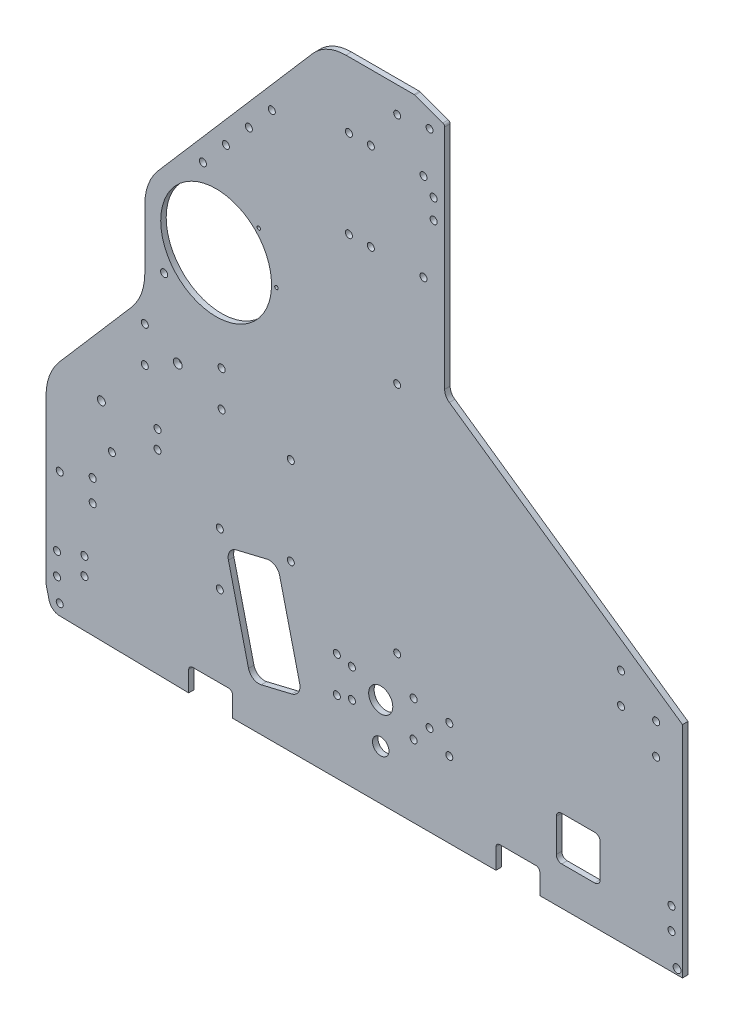
SolidWorks part; units mm, degrees
ref_plane "Front Plane" through (0, 0, 0) normal (0, 0, 1) x (1, 0, 0)
ref_plane "Top Plane" through (0, 0, 0) normal (0, 1, 0) x (1, 0, 0)
ref_plane "Right Plane" through (0, 0, 0) normal (1, 0, 0) x (0, 0, -1)
sketch "Sketch1" plane through (0, 0, 0) normal (0, 0, 1) x (1, 0, 0)
  line L0 (82.55, -20.32) -> (82.55, -6.35)
  line L2 (0, 0) -> (0, 157.48)
  line L4 (368.3, -20.32) -> (368.3, 106.68)
  line L5 (82.55, -6.35) -> (107.95, -6.35)
  line L6 (107.95, -6.35) -> (107.95, -20.32)
  line L7 (107.95, -20.32) -> (260.35, -20.32)
  line L8 (260.35, -20.32) -> (260.35, -6.35)
  line L9 (260.35, -6.35) -> (285.75, -6.35)
  line L10 (285.75, -6.35) -> (285.75, -20.32)
  line L11 (285.75, -20.32) -> (368.3, -20.32)
  line L12 (361.95, 12.7) -> (368.3, 12.7) construction
  line L13 (0, 0) -> (6.35, 0) construction
  line L14 (0.1896, -7.8901) -> (1.7771, -14.2401)
  line L15 (7.8295, -19.0491) -> (82.55, -20.32)
  line L16 (0, 0) -> (0, -6.35)
  line L17 (76.2, 141.605) -> (79.375, 141.605) construction
  line L18 (57.15, 131.2863) -> (101.6, 131.2862) construction
  line L19 (57.15, 131.2863) -> (57.15, 151.9238) construction
  line L20 (101.6, 131.2862) -> (101.6, 151.9237) construction
  line L21 (57.15, 151.9238) -> (101.6, 151.9237) construction
  line L22 (57.15, 131.2863) -> (101.6, 151.9237) construction
  line L23 (101.6, 131.2862) -> (57.15, 151.9238) construction
  line L25 (203.2, 59.805) -> (203.2, 194.805) construction
  line L26 (203.2, 194.805) -> (203.2, 329.805) construction
  line L27 (355.6, 332.105) -> (330.2, 332.105) construction
  line L28 (330.2, 332.105) -> (330.2, 217.805) construction
  line L29 (330.2, 217.805) -> (355.6, 217.805) construction
  line L30 (355.6, 217.805) -> (355.6, 332.105) construction
  line L31 (203.2, 344.805) -> (203.2, 194.805) construction
  line L32 (50.8, 332.105) -> (76.2, 332.105) construction
  line L33 (76.2, 332.105) -> (76.2, 217.805) construction
  line L34 (50.8, 217.805) -> (50.8, 332.105) construction
  line L35 (76.2, 217.805) -> (50.8, 217.805) construction
  line L36 (213.2, 344.805) -> (230.6638, 338.455)
  line L37 (203.2, 344.805) -> (161.925, 344.805)
  line L38 (203.2, 344.805) -> (213.2, 344.805)
  line L39 (348.5362, 344.805) -> (413.4623, 344.805)
  line L40 (348.5362, 344.805) -> (230.6638, 344.805) construction
  line L42 (161.925, 344.805) -> (0, 157.48)
  line L44 (230.6638, 338.455) -> (230.6638, 202.565)
  line L45 (230.6638, 202.565) -> (368.3, 106.68)
  line L46 (213.2, 344.805) -> (-141.0713, 344.805) construction
  circle A0 centre (6.35, 0) radius 2.032
  circle A1 centre (6.35, 12.7) radius 2.032
  circle A2 centre (361.95, 0) radius 2.032
  circle A3 centre (361.95, 12.7) radius 2.032
  arc A5 (1.7771, -14.2401) -> (7.8295, -19.0491) centre (7.9375, -12.7) ccw
  circle A6 centre (7.9375, -12.7) radius 2.032
  arc A7 (0, -6.35) -> (0.1896, -7.8901) centre (6.35, -6.35) ccw
  circle A8 centre (38.1, 78.105) radius 2.032
  circle A9 centre (76.2, 141.605) radius 2.54
  circle A10 centre (101.6, 131.2862) radius 2.032
  circle A11 centre (101.6, 151.9237) radius 2.032
  circle A12 centre (57.15, 151.9238) radius 2.032
  circle A13 centre (57.15, 131.2863) radius 2.032
  circle A15 centre (203.2, 59.805) radius 2
  circle A16 centre (203.2, 194.805) radius 2
  circle A17 centre (203.2, 329.805) radius 2
  circle A18 centre (63.5, 313.055) radius 2.032
  circle A20 centre (355.6, 332.105) radius 2.032
  circle A21 centre (330.2, 332.105) radius 2.032
  circle A22 centre (355.6, 217.805) radius 2.032
  circle A23 centre (330.2, 217.805) radius 2.032
  circle A24 centre (50.8, 332.105) radius 2.032
  circle A25 centre (76.2, 332.105) radius 2.032
  circle A26 centre (50.8, 217.805) radius 2.032
  circle A27 centre (76.2, 217.805) radius 2.032
  circle A28 centre (221.9319, 332.105) radius 2
  circle A29 centre (224.3138, 298.831) radius 2.032
  circle A30 centre (353.06, 100.7351) radius 2.032
  circle A31 centre (332.74, 115.9751) radius 2.032
  circle A32 centre (332.74, 98.1951) radius 2.032
  circle A33 centre (353.06, 82.9551) radius 2.032
  circle A34 centre (117.3562, 280.4276) radius 2.032
  circle A35 centre (104.0678, 265.0548) radius 2.032
  circle A36 centre (90.7795, 249.682) radius 2.032
  circle A38 centre (130.6445, 295.8004) radius 2.032
  circle A39 centre (68.326, 182.9237) radius 2.032
  circle A40 centre (224.3138, 287.401) radius 2.032
  point P82 (203.2, 344.805)
  point P83 (221.9319, 341.63)
  point P90 (368.3, 62.484)
  dimension "D6" = 4.064
  dimension "D10" = 6.35
  dimension "D11" = 4.064
  dimension "D17" = 38.1
  dimension "D27" = 4
  dimension "D31" = 4.064
  dimension "D32" = 41.275
  dimension "D36" = 4.064
  dimension "D47" = 39.624
  dimension "D48" = 4.064
  dimension "D25" = 5.08
  dimension "D26" = 4.064
  dimension "D52" = 4.064
  dimension "D65" = 4.064
  dimension "D2" = 127
  dimension "D3" = 13.97
  dimension "D4" = 25.4
  dimension "D5" = 152.4
  dimension "D7" = 12.7
  dimension "D8" = 6.35
  dimension "D9" = 20.32
  dimension "D12" = 12.7
  dimension "D13" = 1.5875
  dimension "D14" = 82.55
  dimension "D15" = 368.3
  dimension "D16" = 6.35
  dimension "D18" = 98.425
  dimension "D19" = 38.1
  dimension "D20" = 63.5
  dimension "D21" = 3.175
  dimension "D22" = 270
  dimension "D23" = 20.6375
  dimension "D24" = 44.45
  dimension "D28" = 135
  dimension "D29" = 12.7
  dimension "D30" = 15
  dimension "D33" = 63.5
  dimension "D34" = 27.4638
  dimension "D35" = 12.7
  dimension "D37" = 114.3
  dimension "D38" = 25.4
  dimension "D39" = 12.7
  dimension "D40" = 157.48
  dimension "D41" = 142.24
  dimension "D42" = 365.125
  dimension "D43" = 10
  dimension "D44" = 6.35
  dimension "D45" = 31.75
  dimension "D46" = 6.35
  dimension "D49" = 6.35
  dimension "D50" = 203.2
  dimension "D51" = 15.24
  dimension "D53" = 17.78
  dimension "D54" = 17.78
  dimension "D55" = 20.32
  dimension "D56" = 15.24
  dimension "D57" = 92.202
  dimension "D58" = 8.382
  dimension "D59" = 20.32
  dimension "D60" = 20.32
  dimension "D61" = 8.382
  dimension "D62" = 20.32
  dimension "D63" = 8.382
  dimension "D64" = 8.382
  dimension "D66" = 35.052
  dimension "D67" = 68.326
  dimension "D68" = 11.43
extrude "Boss-Extrude1" add sketch "Sketch1" along normal blind 3.175 contours L16 A7 L14 A5 L15 L2 A0 A1 A6 region at (171.3489, 119.5243, 0)
fillet "Fillet1" radius 2.286 4 edges at (285.75, -6.35, 1.5875) (107.95, -6.35, 1.5875) (260.35, -6.35, 1.5875) (82.55, -6.35, 1.5875)
fillet "Fillet2" radius 6.35 1 edges at (230.6638, 202.565, 1.5875)
sketch "Sketch2" plane through (0, 0, 0) normal (0, 0, -1) x (-1, 0, 0)
  circle A0 centre (-100.5528, 71.086) radius 2.032 construction
  circle A1 centre (-100.5528, 40.606) radius 2.032 construction
  circle A2 centre (-22.225, 18.2025) radius 2.032 construction
  circle A3 centre (-22.225, 8.0425) radius 2.032 construction
  circle A4 centre (-100.5528, 71.086) radius 2.032
  circle A5 centre (-100.5528, 40.606) radius 2.032
  circle A6 centre (-22.225, 18.2025) radius 2.032
  circle A7 centre (-22.225, 8.0425) radius 2.032
extrude "Cut-Extrude1" cut sketch "Sketch2" against normal through all
fillet "Fillet3" radius 1.5875 2 edges at (230.6638, 338.455, 1.5875) (213.2, 344.805, 1.5875)
sketch "Sketch3" plane through (0, 0, 3.175) normal (0, 0, 1) x (1, 0, 0)
  line L0 (132.9524, 63.2646) -> (132.7215, 64.2281) construction
  line L1 (128.3814, 66.8897) -> (110.6828, 62.6472) construction
  line L2 (114.5132, 58.4237) -> (126.8822, 61.3887) construction
  line L3 (108.0212, 58.3071) -> (108.2522, 57.3436) construction
  line L4 (131.2006, 57.703) -> (140.0164, 20.9265) construction
  line L5 (144.0993, 16.7636) -> (132.9524, 63.2646) construction
  line L6 (108.2522, 57.3436) -> (119.3991, 10.8426) construction
  line L7 (121.1509, 16.4042) -> (112.3351, 53.1807) construction
  line L8 (119.3991, 10.8426) -> (119.6301, 9.8791) construction
  line L9 (144.3303, 15.8001) -> (144.0993, 16.7636) construction
  line L10 (137.8383, 15.6835) -> (125.4694, 12.7185) construction
  line L11 (123.9701, 7.2175) -> (141.6687, 11.4601) construction
  line L12 (132.9524, 63.2646) -> (132.7215, 64.2281)
  line L13 (128.3814, 66.8897) -> (110.6828, 62.6472)
  line L14 (114.5132, 58.4237) -> (126.8822, 61.3887)
  line L15 (108.0212, 58.3071) -> (108.2522, 57.3436)
  line L16 (131.2006, 57.703) -> (140.0164, 20.9265)
  line L17 (144.0993, 16.7636) -> (132.9524, 63.2646)
  line L18 (108.2522, 57.3436) -> (119.3991, 10.8426)
  line L19 (121.1509, 16.4042) -> (112.3351, 53.1807)
  line L20 (119.3991, 10.8426) -> (119.6301, 9.8791)
  line L21 (144.3303, 15.8001) -> (144.0993, 16.7636)
  line L22 (137.8383, 15.6835) -> (125.4694, 12.7185)
  line L23 (123.9701, 7.2175) -> (141.6687, 11.4601)
  line L24 (127.7894, 69.3598) -> (110.0908, 65.1172)
  line L25 (105.5512, 57.715) -> (105.7822, 56.7515)
  line L26 (105.7822, 56.7515) -> (116.9291, 10.2505)
  line L27 (116.9291, 10.2505) -> (117.16, 9.287)
  line L28 (124.5622, 4.7475) -> (142.2608, 8.99)
  line L29 (146.8003, 16.3922) -> (146.5694, 17.3557)
  line L30 (146.5694, 17.3557) -> (135.4225, 63.8567)
  line L31 (135.4225, 63.8567) -> (135.1915, 64.8202)
  line L32 (14.605, -0.1369) -> (103.7278, 32.3011) construction
  line L33 (14.605, -0.1369) -> (103.7278, 32.3011)
  line L34 (0, -6.35) -> (0, 157.48) construction
  line L35 (-39.6666, 74.7152) -> (103.7278, 126.9065) construction
  line L36 (26.9875, 46.9531) -> (26.9875, 59.6531) construction
  line L37 (107.95, -20.32) -> (260.35, -20.32) construction
  line L38 (64.5259, 92.5258) -> (64.5259, 102.9405) construction
  arc A0 (132.7215, 64.2281) -> (128.6308, 66.9403) centre (129.2206, 63.3889) ccw construction
  arc A1 (110.6828, 62.6472) -> (110.4377, 62.5791) centre (111.522, 59.1463) ccw construction
  arc A2 (128.6308, 66.9403) -> (128.3814, 66.8897) centre (129.2206, 63.3889) ccw construction
  arc A3 (110.4377, 62.5791) -> (108.0212, 58.3071) centre (111.522, 59.1463) ccw construction
  arc A4 (119.6301, 9.8791) -> (123.7207, 7.1669) centre (123.1309, 10.7183) ccw construction
  arc A5 (141.9139, 11.5281) -> (144.3303, 15.8001) centre (140.8295, 14.9609) ccw construction
  arc A6 (141.6687, 11.4601) -> (141.9139, 11.5281) centre (140.8295, 14.9609) ccw construction
  arc A7 (123.7207, 7.1669) -> (123.9701, 7.2175) centre (123.1309, 10.7183) ccw construction
  arc A8 (132.7215, 64.2281) -> (128.6308, 66.9403) centre (129.2206, 63.3889) ccw
  arc A9 (110.6828, 62.6472) -> (110.4377, 62.5791) centre (111.522, 59.1463) ccw
  arc A10 (128.6308, 66.9403) -> (128.3814, 66.8897) centre (129.2206, 63.3889) ccw
  arc A11 (110.4377, 62.5791) -> (108.0212, 58.3071) centre (111.522, 59.1463) ccw
  arc A12 (119.6301, 9.8791) -> (123.7207, 7.1669) centre (123.1309, 10.7183) ccw
  arc A13 (141.9139, 11.5281) -> (144.3303, 15.8001) centre (140.8295, 14.9609) ccw
  arc A14 (141.6687, 11.4601) -> (141.9139, 11.5281) centre (140.8295, 14.9609) ccw
  arc A15 (123.7207, 7.1669) -> (123.9701, 7.2175) centre (123.1309, 10.7183) ccw
  arc A16 (110.0908, 65.1172) -> (109.6726, 65.0012) centre (111.522, 59.1463) ccw
  arc A17 (109.6726, 65.0012) -> (105.5512, 57.715) centre (111.522, 59.1463) ccw
  arc A18 (117.16, 9.287) -> (124.1369, 4.6613) centre (123.1309, 10.7183) ccw
  arc A19 (124.1369, 4.6613) -> (124.5622, 4.7475) centre (123.1309, 10.7183) ccw
  arc A20 (142.2608, 8.99) -> (142.6789, 9.1061) centre (140.8295, 14.9609) ccw
  arc A21 (142.6789, 9.1061) -> (146.8003, 16.3922) centre (140.8295, 14.9609) ccw
  arc A22 (135.1915, 64.8202) -> (128.2147, 69.446) centre (129.2206, 63.3889) ccw
  arc A23 (128.2147, 69.446) -> (127.7894, 69.3598) centre (129.2206, 63.3889) ccw
  circle A26 centre (133.35, 208.2281) radius 1.016 construction
  circle A33 centre (26.9875, 46.9531) radius 2.032
  circle A34 centre (26.9875, 59.6531) radius 2.032
  circle A35 centre (7.9375, 53.3031) radius 2.032
  circle A37 centre (32.0306, 100.8109) radius 31.75 construction
  circle A38 centre (32.0306, 100.8109) radius 2.286
  circle A39 centre (123.1207, 232.9238) radius 1.016 construction
  circle A40 centre (64.5259, 102.9405) radius 2.032
  circle A41 centre (64.5259, 92.5258) radius 2.032
  circle A42 centre (133.35, 208.2281) radius 1.016
  circle A43 centre (123.1207, 232.9238) radius 1.016
  ellipse E0 centre (124.5974, 48.8487) end of major axis (128.5376, 61.3578) minor radius 6 (131.2006, 57.703) -> (126.8822, 61.3887) ccw construction
  ellipse E1 centre (122.2349, 48.2824) end of major axis (113.0518, 57.6456) minor radius 6 (114.5132, 58.4237) -> (112.3351, 53.1807) ccw construction
  ellipse E2 centre (127.7541, 25.2585) end of major axis (131.6942, 37.7675) minor radius 6 (121.1509, 16.4042) -> (125.4694, 12.7185) ccw construction
  ellipse E3 centre (130.1166, 25.8248) end of major axis (139.2998, 16.4616) minor radius 6 (137.8383, 15.6835) -> (140.0164, 20.9265) ccw construction
  ellipse E4 centre (124.5974, 48.8487) end of major axis (120.6573, 36.3397) minor radius 6 (131.2006, 57.703) -> (126.8822, 61.3887) ccw
  ellipse E5 centre (122.2349, 48.2824) end of major axis (131.4181, 38.9192) minor radius 6 (114.5132, 58.4237) -> (112.3351, 53.1807) ccw
  ellipse E6 centre (127.7541, 25.2585) end of major axis (131.6942, 37.7675) minor radius 6 (121.1509, 16.4042) -> (125.4694, 12.7185) ccw
  ellipse E7 centre (130.1166, 25.8248) end of major axis (139.2998, 16.4616) minor radius 6 (137.8383, 15.6835) -> (140.0164, 20.9265) ccw
  point P93 (26.9875, 53.3031)
  point P115 (32.0306, 100.8109)
  dimension "D3" = 63.5
  dimension "D4" = 4.572
  dimension "D8" = 4.064
  dimension "D2" = 88.9
  dimension "D5" = 7.9375
  dimension "D6" = 19.05
  dimension "D7" = 73.6231
  dimension "D9" = 12.7
  dimension "D10" = 10.4147
  dimension "D11" = 37.5384
  dimension "D12" = 45.5727
  dimension "D1" = 2.54
extrude "Cut-Extrude2" cut sketch "Sketch3" against normal through all contours A22 A23 L24 A16 A17 L25 L26 L27 A18 A19 L28 A20 A21 L29 L30 L31 A15 A12 L20 L18 L15 A11 A9 L13 A10 A8 L12 L17 L21 A13 A14 L23 | A12 A15 L23 A14 A13 L21 L17 L12 A8 A10 L13 A9 A11 L15 L18 L20 E7 L22 E6 L19 E5 L14 E4 L16 | L22 E7 L16 E4 L14 E5 L19 E6 | A38 | A41 | A40 | A35 | A34 | A33 | A43 | A42 region at (137.844, 39.8506, 3.175) region at (126.1758, 37.0536, 3.175) region at (128.1544, 68.6507, 3.175) region at (32.0306, 100.8109, 3.175) region at (64.5259, 102.9405, 3.175) region at (64.5259, 92.5258, 3.175)
sketch "Sketch4" plane through (0, 0, 3.175) normal (0, 0, 1) x (1, 0, 0)
  line L0 (57.15, 151.9238) -> (101.6, 151.9237) construction
  line L1 (168.275, 21.4312) -> (212.725, 21.4312) construction
  line L2 (168.275, 21.4312) -> (168.275, 42.0687) construction
  line L3 (168.275, 42.0687) -> (212.725, 42.0687) construction
  line L4 (212.725, 21.4312) -> (212.725, 42.0687) construction
  line L5 (168.275, 21.4312) -> (212.725, 42.0687) construction
  line L6 (168.275, 42.0687) -> (212.725, 21.4312) construction
  line L7 (57.15, 131.2863) -> (57.15, 151.9238) construction
  line L8 (107.95, -20.32) -> (260.35, -20.32) construction
  line L9 (193.675, 31.75) -> (177.005, 31.75) construction
  line L10 (190.5, 31.75) -> (193.675, 31.75) construction
  line L11 (6.35, 12.7) -> (361.95, 12.7) construction
  line L12 (107.95, -6.35) -> (107.95, -20.32) construction
  line L13 (193.675, 31.75) -> (220.6625, 31.75) construction
  line L14 (177.005, 23.4569) -> (177.005, 40.0431) construction
  line L15 (213.2, 44.805) -> (193.2, 44.805) construction
  line L16 (213.2, 44.805) -> (213.2, 344.805) construction
  line L17 (213.2, 344.805) -> (193.2, 344.805) construction
  line L18 (193.2, 44.805) -> (193.2, 344.805) construction
  line L19 (213.2, 44.805) -> (193.2, 344.805) construction
  line L20 (213.2, 344.805) -> (193.2, 44.805) construction
  line L21 (226.9319, 332.105) -> (226.9319, 31.75) construction
  line L22 (237.33, 40.0431) -> (233.3612, 40.0431) construction
  line L23 (237.33, 23.4569) -> (233.3612, 23.4569) construction
  circle A0 centre (168.275, 42.0687) radius 2.032
  circle A1 centre (212.725, 42.0687) radius 2.032
  circle A2 centre (212.725, 21.4312) radius 2.032
  circle A3 centre (168.275, 21.4312) radius 2.032
  circle A4 centre (193.675, 31.75) radius 6.985
  circle A7 centre (220.6625, 31.75) radius 14.2875 construction
  circle A8 centre (193.675, 31.75) radius 12.7 construction
  circle A9 centre (177.005, 40.0431) radius 2.032
  circle A10 centre (177.005, 23.4569) radius 2.032
  circle A11 centre (237.33, 40.0431) radius 2.032 construction
  circle A12 centre (237.33, 23.4569) radius 2.032 construction
  circle A13 centre (193.675, 8.4667) radius 4.7625
  circle A14 centre (221.9319, 31.75) radius 2.032
  circle A15 centre (221.9319, 31.75) radius 5 construction
  circle A16 centre (221.9319, 332.105) radius 5 construction
  circle A17 centre (233.3612, 23.4569) radius 2.032
  circle A18 centre (233.3612, 40.0431) radius 2.032
  point P0 (190.5, 31.75)
  point P26 (203.2, 194.805)
  point P38 (177.005, 31.75)
  dimension "D1" = 4.064
  dimension "D4" = 13.97
  dimension "D7" = 9.525
  dimension "D10" = 25.4
  dimension "D11" = 28.575
  dimension "D16" = 10
  dimension "D17" = 4.064
  dimension "D18" = 10
  dimension "D2" = 52.07
  dimension "D3" = 3.175
  dimension "D5" = 82.55
  dimension "D6" = 26.9875
  dimension "D8" = 20
  dimension "D9" = 300
  dimension "D12" = 16.67
  dimension "D13" = 16.5862
  dimension "D14" = 60.325
  dimension "D15" = 23.2833
  dimension "D19" = 3.9688
extrude "Cut-Extrude3" cut sketch "Sketch4" against normal through all
sketch "Sketch5" plane through (0, 0, 0) normal (0, 0, -1) x (-1, 0, 0)
  line L0 (-57.15, 223.5947) -> (-57.15, 165.3337)
  line L1 (-161.925, 344.805) -> (-52.7201, 218.4699) construction
  line L2 (-57.15, 165.3337) -> (0, 99.219)
  line L3 (0, -6.35) -> (0, 157.48) construction
  line L5 (-50.4199, 215.8089) -> (0, 157.48) construction
  line L6 (-57.15, 223.5947) -> (0, 157.48)
  line L7 (0, 157.48) -> (0, 99.219)
  line L8 (-365.1708, -17.1908) -> (-368.3, -17.1908) construction
  line L9 (-365.1708, -17.1908) -> (-365.1708, -20.32) construction
  line L10 (-285.75, -20.32) -> (-368.3, -20.32) construction
  line L11 (-368.3, -20.32) -> (-368.3, 106.68) construction
  circle A0 centre (-98.425, 208.2281) radius 32.0675
  circle A2 centre (-365.1708, -17.1908) radius 2.286
  dimension "D3" = 64.135
  dimension "D7" = 4.572
  dimension "D1" = 38.1
  dimension "D2" = 57.15
  dimension "D4" = 41.275
  dimension "D5" = 41.275
  dimension "D6" = 3.1292
extrude "Cut-Extrude5" cut sketch "Sketch5" against normal through all contours A0 | L7 L6 L0 L2 | A2 region at (28.575, 161.4068, 0) region at (98.425, 208.2281, 0)
fillet "Fillet4" radius 31.75 3 edges at (0, 99.219, 1.5875) (57.15, 165.3337, 1.5875) (57.15, 223.5947, 1.5875)
sketch "Sketch6" plane through (0, 0, 3.175) normal (0, 0, 1) x (1, 0, 0)
  line L0 (285.75, -20.32) -> (368.3, -20.32) construction
  line L1 (298.45, 27.305) -> (317.5, 27.305)
  line L2 (295.275, 24.13) -> (295.275, 5.08)
  line L3 (298.45, 1.905) -> (317.5, 1.905)
  line L4 (320.675, 24.13) -> (320.675, 5.08)
  line L5 (295.275, 27.305) -> (320.675, 1.905) construction
  line L6 (295.275, 1.905) -> (320.675, 27.305) construction
  line L7 (368.3, -20.32) -> (368.3, 106.68) construction
  arc A0 (295.275, 5.08) -> (298.45, 1.905) centre (298.45, 5.08) ccw
  arc A1 (317.5, 1.905) -> (320.675, 5.08) centre (317.5, 5.08) ccw
  arc A2 (317.5, 27.305) -> (320.675, 24.13) centre (317.5, 24.13) cw
  arc A3 (298.45, 27.305) -> (295.275, 24.13) centre (298.45, 24.13) ccw
  point P0 (307.975, 14.605)
  dimension "D2" = 3.175
  dimension "D1" = 25.4
  dimension "D3" = 22.225
  dimension "D4" = 47.625
extrude "Cut-Extrude6" cut sketch "Sketch6" against normal through all
fillet "Fillet5" radius 25.4 1 edges at (161.925, 344.805, 1.5875)
sketch "Sketch8" plane through (0, 0, 0) normal (0, 0, -1) x (-1, 0, 0)
  circle A0 centre (-187.96, 306.705) radius 2.032 construction
  arc A1 (-176.3652, 304.9998) -> (-176.3652, 308.4102) centre (-175.26, 306.705) ccw construction
  arc A2 (-219.0586, 304.7695) -> (-219.0586, 308.6405) centre (-218.44, 306.705) ccw construction
  circle A3 centre (-205.74, 306.705) radius 2.032 construction
  arc A4 (-219.0586, 253.9695) -> (-219.0586, 257.8405) centre (-218.44, 255.905) ccw construction
  circle A5 centre (-205.74, 255.905) radius 2.032 construction
  circle A6 centre (-187.96, 255.905) radius 2.032 construction
  arc A7 (-176.3652, 254.1998) -> (-176.3652, 257.6102) centre (-175.26, 255.905) ccw construction
  circle A8 centre (-187.96, 306.705) radius 2.032
  arc A9 (-176.3652, 304.9998) -> (-176.3652, 308.4102) centre (-175.26, 306.705) ccw
  arc A10 (-219.0586, 304.7695) -> (-219.0586, 308.6405) centre (-218.44, 306.705) ccw
  circle A11 centre (-205.74, 306.705) radius 2.032
  arc A12 (-219.0586, 253.9695) -> (-219.0586, 257.8405) centre (-218.44, 255.905) ccw
  circle A13 centre (-205.74, 255.905) radius 2.032
  circle A14 centre (-187.96, 255.905) radius 2.032
  arc A15 (-176.3652, 254.1998) -> (-176.3652, 257.6102) centre (-175.26, 255.905) ccw
  circle A16 centre (-218.44, 306.705) radius 2.032
  circle A17 centre (-175.26, 306.705) radius 2.032
  circle A18 centre (-175.26, 255.905) radius 2.032
  circle A19 centre (-218.44, 255.905) radius 2.032
  circle A20 centre (-218.44, 306.705) radius 3.9687
  circle A21 centre (-205.74, 306.705) radius 3.9687
  circle A22 centre (-175.26, 306.705) radius 3.9687
  circle A23 centre (-218.44, 255.905) radius 3.9687
  circle A24 centre (-205.74, 255.905) radius 3.9687
  circle A25 centre (-187.96, 255.905) radius 3.9687
  circle A26 centre (-175.26, 255.905) radius 3.9687
  circle A27 centre (-187.96, 306.705) radius 3.9687
  dimension "D1" = 7.9375
extrude "Cut-Extrude7" cut sketch "Sketch8" against normal through all contours A10 A16 | A9 A17 | A15 A18 | A12 A19 | A8 | A14 region at (175.26, 306.705, 0) region at (218.44, 306.705, 0) region at (218.44, 255.905, 0) region at (175.26, 255.905, 0)
sketch "Sketch10" plane through (0, 0, 3.175) normal (0, 0, 1) x (1, 0, 0)
  circle A4 centre (141.6425, 75.1606) radius 2.032 construction
  circle A5 centre (141.6425, 125.9606) radius 2.032 construction
  circle A6 centre (141.6425, 75.1606) radius 2.032
  circle A7 centre (141.6425, 125.9606) radius 2.032
extrude "Cut-Extrude8" cut sketch "Sketch10" against normal through all
